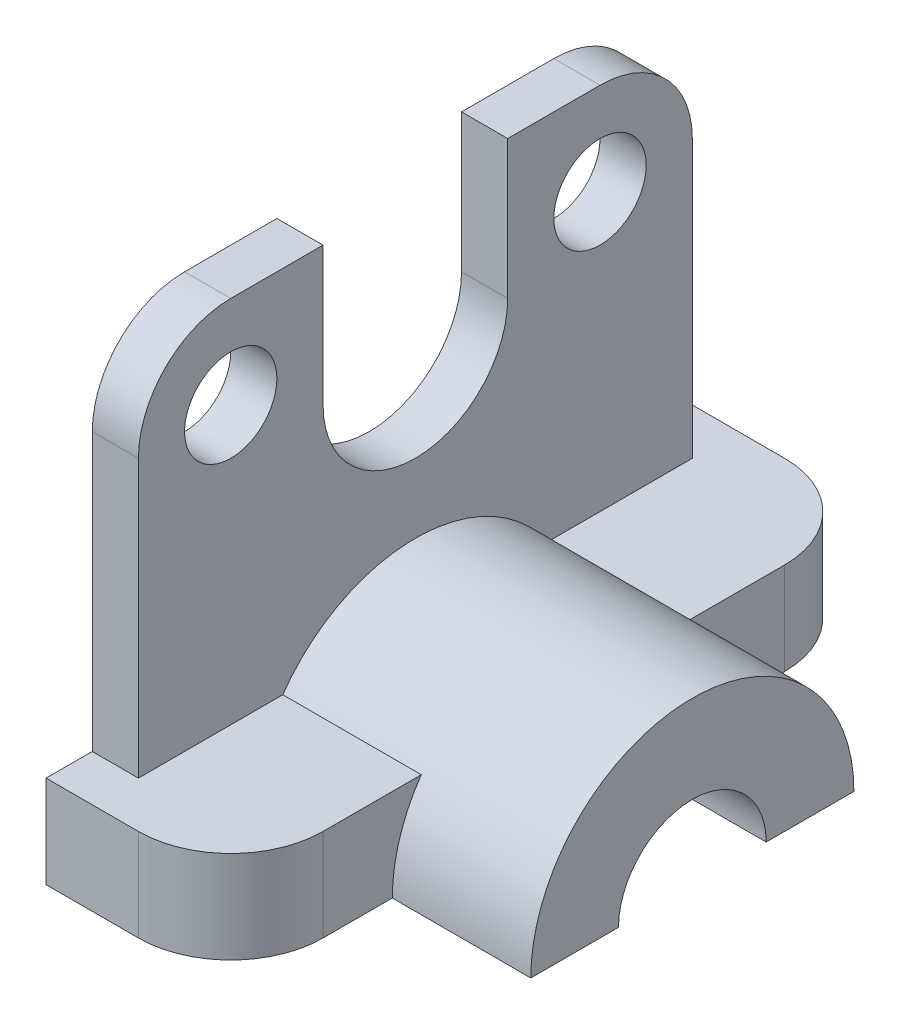
SolidWorks part; units mm, degrees
ref_plane "前基準面" through (0, 0, 0) normal (0, 0, 1) x (1, 0, 0)
ref_plane "上基準面" through (0, 0, 0) normal (0, 1, 0) x (1, 0, 0)
ref_plane "右基準面" through (0, 0, 0) normal (1, 0, 0) x (0, 0, -1)
sketch "草圖1" plane through (0, 0, 0) normal (1, 0, 0) x (0, 0, -1)
  line L0 (0, 0) -> (70, 0)
  line L1 (70, 0) -> (70, -10)
  line L2 (70, -10) -> (0, -10)
  line L3 (0, -10) -> (0, 0)
  line L4 (5, 0) -> (5, 30)
  line L5 (15, 40) -> (25, 40)
  line L6 (25, 40) -> (25, 25)
  line L8 (35, -30.864) -> (35, 68.6888) construction
  line L9 (45, 40) -> (45, 25)
  line L10 (55, 40) -> (45, 40)
  line L11 (65, 0) -> (65, 30)
  arc A0 (55, 40) -> (65, 30) centre (55, 30) cw
  arc A1 (5, 30) -> (15, 40) centre (15, 30) cw
  arc A2 (25, 25) -> (45, 25) centre (35, 25) ccw
  point P13 (35, 34.2787)
  point P18 (65, 40)
  point P21 (5, 40)
  dimension "D1" = 10
  dimension "D7" = 15
  dimension "D2" = 20
  dimension "D3" = 70
  dimension "D4" = 60
  dimension "D5" = 30
  dimension "D6" = 10
extrude "填料-伸長1" add sketch "草圖1" along normal blind 20 contours L2 L8 L0 L3 | L8 L2 L1 L0 region at (0, -5, -17.5) region at (0, -5, -52.5)
extrude "填料-伸長2" add sketch "草圖1<3>" along normal blind 5 contours L0 L8 A2 L6 L5 A1 L4 | L8 L0 L11 A0 L10 L9 A2 region at (0, 17.5625, -17.8202) region at (0, 17.5625, -52.1798)
sketch "草圖1<3>" plane through (0, 0, 0) normal (1, 0, 0) x (0, 0, -1) same geometry as "草圖1"
fillet "圓角1" radius 10 2 edges at (20, -5, -70) (20, -5, 0)
sketch "草圖2" plane through (5, 0, 0) normal (1, 0, 0) x (0, 0, -1)
  line L0 (35, 15) -> (35, 5.5308) construction
  circle A0 centre (15, 30) radius 5
  arc A1 (25, 25) -> (45, 25) centre (35, 25) ccw construction
  circle A2 centre (55, 30) radius 5
  dimension "D1" = 10
extrude "除料-伸長1" cut sketch "草圖2" against normal through all
sketch "草圖3" plane through (0, 0, 0) normal (1, 0, 0) x (0, 0, -1)
  line L0 (60, -10) -> (10, -10) construction
  line L1 (17.5, -10) -> (27, -10)
  line L2 (43, -10) -> (52.5, -10)
  arc A0 (43, -10) -> (27, -10) centre (35, -10) ccw
  arc A1 (52.5, -10) -> (17.5, -10) centre (35, -10) ccw
  dimension "D1" = 16
  dimension "D2" = 35
extrude "填料-伸長5" add sketch "草圖3" against normal up to surface (-5 mm away) from offset 35 up to face at (5, 30, -50)
sketch "草圖5" plane through (20, 0, 0) normal (1, 0, 0) x (0, 0, -1)
  line L0 (43, -10) -> (27, -10) construction
  circle A0 centre (35, -10) radius 8
extrude "除料-伸長2" cut sketch "草圖5" against normal through all
